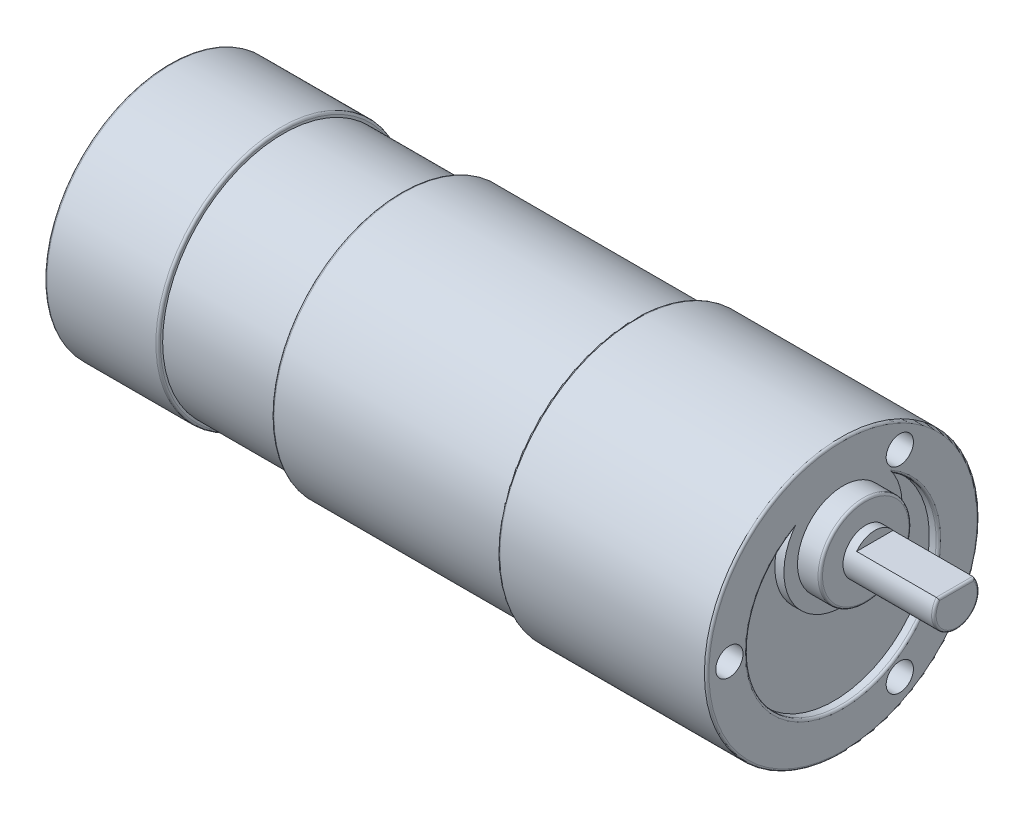
SolidWorks part; units mm, degrees
other "Camera1"
material "1060 Alloy"
ref_plane "Front Plane" through (0, 0, 0) normal (0, 0, 1) x (1, 0, 0)
ref_plane "Top Plane" through (0, 0, 0) normal (0, 1, 0) x (1, 0, 0)
ref_plane "Right Plane" through (0, 0, 0) normal (1, 0, 0) x (0, 0, -1)
sketch "Sketch1" plane through (0, 0, 0) normal (1, 0, 0) x (0, 0, -1)
  circle A0 centre (0, 0) radius 15
  dimension "D1" = 30
extrude "Boss-Extrude1" add sketch "Sketch1" along normal blind 76.6
sketch "Sketch2" plane through (76.6, 0, 0) normal (1, 0, 0) x (0, 0, -1)
  line L0 (0, 0) -> (0, 5.5) construction
  circle A0 centre (0, 5.5) radius 2.5
  dimension "D1" = 5
  dimension "D2" = 5.5
extrude "Boss-Extrude2" add sketch "Sketch2" along normal blind 10
sketch "Sketch4" plane through (86.6, 0, 0) normal (1, 0, 0) x (0, 0, -1)
  line L0 (-2, 7) -> (2, 7)
  line L1 (0, 5.5) -> (0, 7) construction
  arc A0 (2, 7) -> (-2, 7) centre (0, 5.5) ccw
  circle A1 centre (0, 5.5) radius 2.5 construction
  dimension "D1" = 1.5
extrude "Cut-Extrude1" cut sketch "Sketch4" against normal blind 9
sketch "Sketch5" plane through (0, 0, 0) normal (0, 0, 1) x (1, 0, 0)
  line L0 (0, 0) -> (76.6, 0) construction
  line L1 (76.6, -15) -> (76.6, 15) construction
  line L2 (76.6, 5.5) -> (86.6, 5.5) construction
  line L3 (76.6, 3) -> (76.6, 8) construction
  line L4 (86.6, 3) -> (86.6, 7) construction
  line L6 (0, 13.75) -> (12.5, 13.75)
  line L7 (0, 15) -> (0, -15) construction
  line L8 (12.5, 13.75) -> (12.5, 13.25)
  line L9 (12.5, 13.25) -> (25.5, 13.25)
  line L10 (25.5, 13.25) -> (25.5, 14.25)
  line L11 (25.5, 14.25) -> (51.1, 14.25)
  line L12 (51.1, 14.25) -> (51.1, 15)
  line L13 (76.6, 15) -> (0, 15) construction
  line L14 (51.1, 15) -> (0, 15)
  line L15 (0, 15) -> (0, 13.75)
  dimension "D1" = 0.75
  dimension "D2" = 1.25
  dimension "D3" = 0.5
  dimension "D4" = 12.5
  dimension "D5" = 13
  dimension "D6" = 25.6
ref_axis "Axis1" through (-4.33, 0, 0) along (1, 0, 0)
revolve "Cut-Revolve1" cut sketch "Sketch5" angle 360 about axis through (-4.33, 0, 0) along (1, 0, 0)
sketch "Sketch6" plane through (76.6, 0, 0) normal (1, 0, 0) x (0, 0, -1)
  circle A0 centre (0, 0) radius 15
  circle A1 centre (0, 5.5) radius 5
  dimension "D1" = 10
  dimension "D2" = 30
extrude "Cut-Extrude2" cut sketch "Sketch6" against normal blind 2.5
sketch "Sketch7" plane through (74.1, 0, 0) normal (1, 0, 0) x (0, 0, -1)
  circle A0 centre (0, 0) radius 10.5
  circle A1 centre (0, 5.5) radius 6.5
  circle A2 centre (0, 5.5) radius 5 construction
  dimension "D1" = 1.5
extrude "Cut-Extrude3" cut sketch "Sketch7" against normal blind 1 contours A1 A0 region at (74.1, -2.6501, 0)
sketch "Sketch8" plane through (74.1, 0, 0) normal (1, 0, 0) x (0, 0, -1)
  line L0 (0, 0) -> (15, 0) construction
  line L1 (0, 0) -> (6.25, 10.8253) construction
  circle A0 centre (0, 0) radius 12.5 construction
  circle A1 centre (6.25, 10.8253) radius 1.5
  circle A2 centre (0, 0) radius 15 construction
  circle A3 centre (6.25, -10.8253) radius 1.5
  circle A4 centre (-12.5, 0) radius 1.5
  dimension "D1" = 25
  dimension "D3" = 3
  dimension "D2" = 60
  dimension "D4" = 3
extrude "Cut-Extrude4" cut sketch "Sketch8" against normal blind 4
fillet "Fillet1" radius 0.25 9 edges at (86.6, 7, 0) (86.6, 3, 0) (76.6, 5.5, -5) (12.5, 0, 13.75) (25.5, 0, 14.25) (51.1, 0, 15) (0, 0, 13.75) (74.1, 0, -15) (74.1, -10.5, 0)
